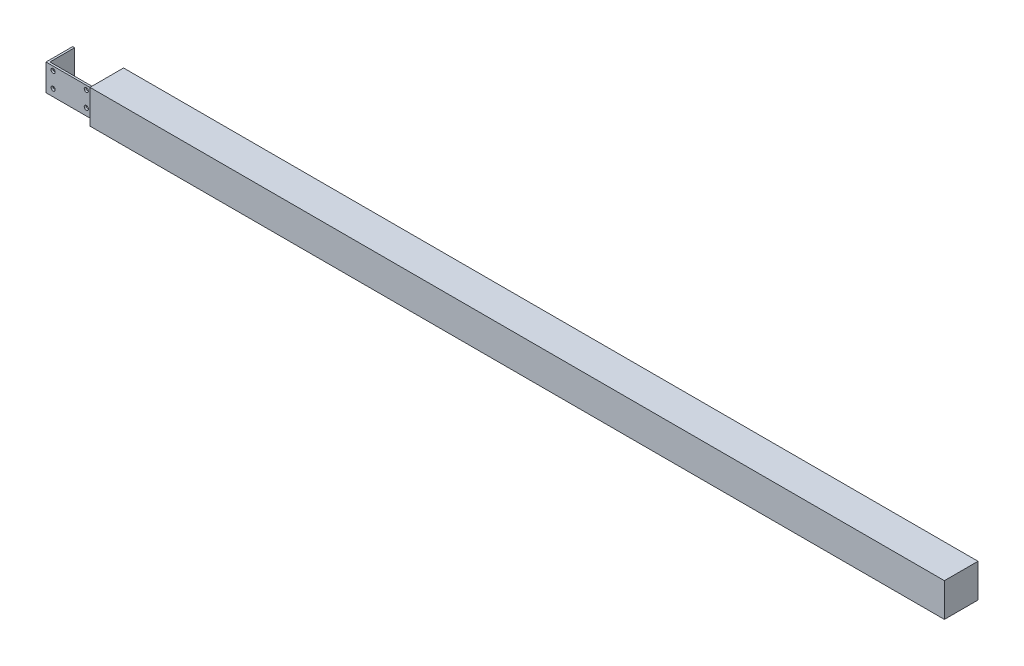
SolidWorks part; units mm, degrees
material "1023 Carbon Steel Sheet (SS)"
ref_plane "Front Plane" through (0, 0, 0) normal (0, 0, 1) x (1, 0, 0)
ref_plane "Top Plane" through (0, 0, 0) normal (0, 1, 0) x (1, 0, 0)
ref_plane "Right Plane" through (0, 0, 0) normal (1, 0, 0) x (0, 0, -1)
sketch "Sketch1" plane through (0, 0, 0) normal (0, 0, 1) x (1, 0, 0)
  line L264 (-103.7607, 63.7322) -> (-103.7607, -66.2678)
  line L265 (116.2393, 63.7322) -> (116.2393, -66.2678)
  line L267 (116.2393, 63.7322) -> (-103.7607, 63.7322)
  line L269 (116.2393, -66.2678) -> (-103.7607, -66.2678)
  circle A2 centre (90.2393, -40.2678) radius 10.5
  circle A3 centre (-77.7607, -40.2678) radius 10.5
  circle A4 centre (-77.7607, 37.7322) radius 10.5
  circle A5 centre (90.2393, 37.7322) radius 10.5
extrude "Boss-Extrude1" add sketch "Sketch1" along normal blind 10
sketch "Sketch2" plane through (0, 0, 10) normal (0, 0, 1) x (1, 0, 0)
  line L3 (-103.7607, 63.7322) -> (-113.7607, 63.7322)
  line L4 (-103.7607, 63.7322) -> (-103.7607, -66.2678)
  line L6 (-113.7607, 63.7322) -> (-113.7607, -66.2678)
  line L7 (-103.7607, -66.2678) -> (116.2393, -66.2678)
  line L8 (-113.7607, -66.2678) -> (-113.7607, -76.2678)
  line L9 (-113.7607, -76.2678) -> (116.2393, -76.2678)
  line L10 (116.2393, -66.2678) -> (116.2393, -76.2678)
extrude "Boss-Extrude2" add sketch "Sketch2" against normal blind 250
sketch "Sketch3" plane through (0, 63.7322, 0) normal (0, 1, 0) x (1, 0, 0)
  line L6 (116.2393, 0) -> (-103.7607, 0)
  line L7 (-103.7607, 0) -> (-103.7607, 240)
  line L8 (-103.7607, 240) -> (-113.7607, 240)
  line L9 (-113.7607, 240) -> (-113.7607, -10)
  line L10 (-113.7607, -10) -> (116.2393, -10)
  line L11 (116.2393, -10) -> (116.2393, 0)
  line L12 (116.2393, 0) -> (-103.7607, 0)
  line L13 (-103.7607, 0) -> (-103.7607, 240)
  line L14 (-103.7607, 240) -> (-113.7607, 240)
  line L15 (-113.7607, 240) -> (-113.7607, -10)
  line L16 (-113.7607, -10) -> (116.2393, -10)
  line L17 (116.2393, -10) -> (116.2393, 0)
  dimension "D1" = 0
extrude "Cut-Extrude1" cut sketch "Sketch3" against normal blind 5
sketch "Sketch4" plane through (0, 0, 10) normal (0, 0, 1) x (1, 0, 0)
  line L0 (-113.7607, -76.2678) -> (116.2393, -76.2678) construction
  line L1 (-113.7607, -76.2678) -> (116.2393, -76.2678)
  line L3 (116.2393, 58.7322) -> (126.2393, 58.7322)
  line L4 (116.2393, 58.7322) -> (116.2393, -76.2678)
  line L5 (116.2393, -76.2678) -> (126.2393, -76.2678)
  line L6 (126.2393, 58.7322) -> (126.2393, -76.2678)
  line M5 (116.2393, -76.2678) -> (116.2393, 58.7322)
extrude "Boss-Extrude3" add sketch "Sketch4" against normal up to surface (250 mm away) contours L6 L3 L5 M5 region at (121.2393, -8.7678, 10) up to face at (-33.7607, -27.9344, -240)
sketch "Sketch5" plane through (126.2393, 0, 0) normal (1, 0, 0) x (0, 0, -1)
  line L4 (240, -76.2678) -> (240, 58.7322)
  line L5 (240, 58.7322) -> (-10, 58.7322)
  line L6 (-10, 58.7322) -> (-10, -76.2678)
  line L7 (-10, -76.2678) -> (240, -76.2678)
  line L8 (240, -76.2678) -> (240, 58.7322)
  line L9 (240, 58.7322) -> (-10, 58.7322)
  line L10 (-10, 58.7322) -> (-10, -76.2678)
  line L11 (-10, -76.2678) -> (240, -76.2678)
  dimension "D1" = 0
extrude "Boss-Extrude4" add sketch "Sketch5" along normal blind 2800 separate body
sketch "Sketch8" plane through (2926.2393, 0, 0) normal (1, 0, 0) x (0, 0, -1)
  line L0 (-10, -76.2678) -> (240, -76.2678) construction
  line L1 (-10, 58.7322) -> (125, 58.7322)
  line L2 (-10, 58.7322) -> (-10, -76.2678)
  line L3 (-10, -76.2678) -> (125, -76.2678)
  line L4 (125, 58.7322) -> (125, -76.2678)
  line L6 (125, 58.7322) -> (240, 58.7322)
  line L7 (125, 58.7322) -> (125, -76.2678)
  line L8 (125, -76.2678) -> (240, -76.2678)
  line L9 (240, 58.7322) -> (240, -76.2678)
  line M9 (-10, -76.2678) -> (240, -76.2678)
  line M10 (240, -76.2678) -> (240, 58.7322)
  line M11 (240, 58.7322) -> (-10, 58.7322)
extrude "Cut-Extrude2" cut sketch "Sketch8" against normal blind 10000 contours L4 M11 M9 M10 region at (2926.2393, -8.7678, -182.5)
sketch "Sketch12" plane through (2926.2393, 0, 0) normal (1, 0, 0) x (0, 0, -1)
  line L2 (-27.5, 76.2322) -> (142.5, 76.2322)
  line L3 (-27.5, 76.2322) -> (-27.5, -93.7678)
  line L4 (-27.5, -93.7678) -> (142.5, -93.7678)
  line L5 (142.5, 76.2322) -> (142.5, -93.7678)
  line L6 (-27.5, 76.2322) -> (142.5, -93.7678) construction
  line L7 (-27.5, -93.7678) -> (142.5, 76.2322) construction
  point P4 (57.5, -8.7678)
extrude "Boss-Extrude6" add sketch "Sketch12" against normal up to vertex (2800 mm away) up to point (126.2393, 58.7322, 10)
sketch "Sketch14" plane through (0, -76.2678, 0) normal (0, -1, 0) x (1, 0, 0)
  line L0 (-103.7607, 0) -> (116.2393, 0)
  line L5 (116.2393, 0) -> (116.2393, -115)
  line L7 (-103.7607, 0) -> (-103.7607, -115)
  line L8 (116.2393, -115) -> (116.2393, -125)
  line L12 (116.2393, -125) -> (-103.7607, -125)
  line L13 (-103.7607, -125) -> (-103.7607, -115)
extrude "Cut-Extrude3" cut sketch "Sketch14" against normal blind 50
sketch "Sketch15" plane through (2926.2393, 0, 0) normal (1, 0, 0) x (0, 0, -1)
  line L4 (142.5, -93.7678) -> (142.5, 76.2322)
  line L5 (142.5, 76.2322) -> (-27.5, 76.2322)
  line L6 (-27.5, 76.2322) -> (-27.5, -93.7678)
  line L7 (-27.5, -93.7678) -> (142.5, -93.7678)
  line L8 (142.5, -93.7678) -> (142.5, 76.2322)
  line L9 (142.5, 76.2322) -> (-27.5, 76.2322)
  line L10 (-27.5, 76.2322) -> (-27.5, -93.7678)
  line L11 (-27.5, -93.7678) -> (142.5, -93.7678)
  dimension "D1" = 0
extrude "Boss-Extrude7" add sketch "Sketch15" along normal blind 1524
